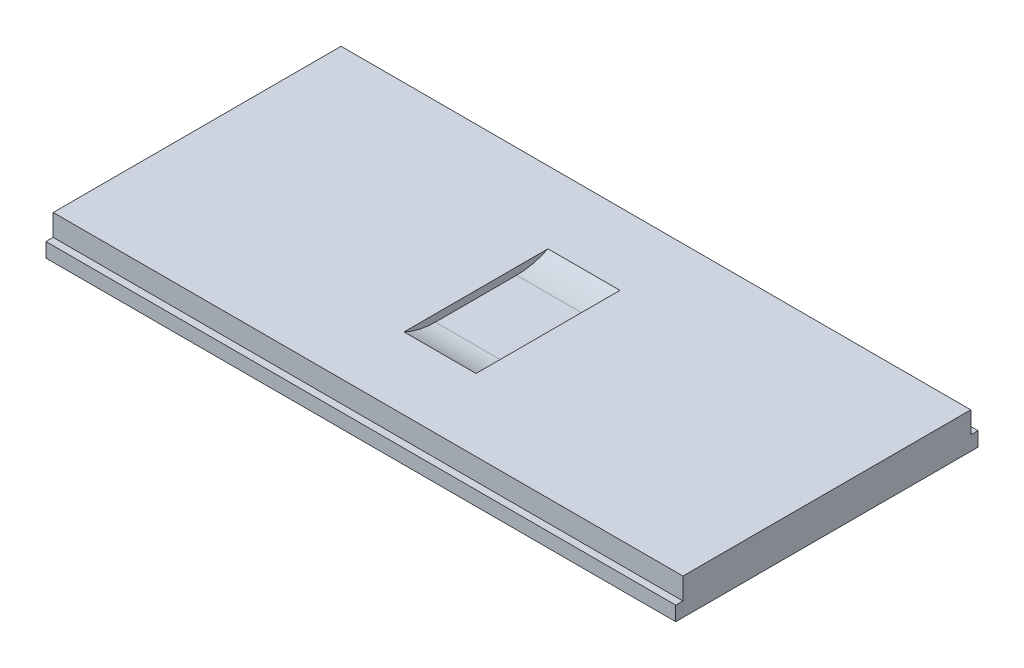
SolidWorks part; units mm, degrees
ref_plane "Front Plane" through (0, 0, 0) normal (0, 0, 1) x (1, 0, 0)
ref_plane "Top Plane" through (0, 0, 0) normal (0, 1, 0) x (1, 0, 0)
ref_plane "Right Plane" through (0, 0, 0) normal (1, 0, 0) x (0, 0, -1)
sketch "Sketch1" plane through (0, 0, 0) normal (0, 1, 0) x (1, 0, 0)
  line L1 (-43.75, 21) -> (43.75, 21)
  line L2 (-43.75, 21) -> (-43.75, -21)
  line L3 (-43.75, -21) -> (43.75, -21)
  line L4 (43.75, 21) -> (43.75, -21)
  line L5 (-43.75, 21) -> (43.75, -21) construction
  line L6 (-43.75, -21) -> (43.75, 21) construction
  point P0 (0, 0)
extrude "Boss-Extrude1" add sketch "Sketch1" along normal blind 5
sketch "Sketch2" plane through (0, 5, 0) normal (0, 1, 0) x (1, 0, 0)
  line L0 (-43.75, 21) -> (-43.75, -21) construction
  line L1 (43.75, 21) -> (-43.75, 21)
  line L2 (43.75, 21) -> (43.75, 20)
  line L3 (43.75, 20) -> (-43.75, 20)
  line L4 (-43.75, 21) -> (-43.75, 20)
extrude "Cut-Extrude1" cut sketch "Sketch2" against normal blind 3
sketch "Sketch3" plane through (0, 5, 0) normal (0, 1, 0) x (1, 0, 0)
  line L0 (43.75, -21) -> (43.75, 20) construction
  line L1 (-43.75, -21) -> (43.75, -21)
  line L2 (-43.75, -21) -> (-43.75, -20)
  line L3 (-43.75, -20) -> (43.75, -20)
  line L4 (43.75, -21) -> (43.75, -20)
extrude "Cut-Extrude2" cut sketch "Sketch3" against normal blind 3
sketch "Sketch4" plane through (0, 5, 0) normal (0, 1, 0) x (1, 0, 0)
  line L1 (-5, 10) -> (5, 10)
  line L2 (-5, 10) -> (-5, -10)
  line L3 (-5, -10) -> (5, -10)
  line L4 (5, 10) -> (5, -10)
  line L5 (-5, 10) -> (5, -10) construction
  line L6 (-5, -10) -> (5, 10) construction
  point P0 (0, 0)
extrude "Cut-Extrude3" cut sketch "Sketch4" against normal blind 1
fillet "Fillet1" radius 10 1 edges at (0, 4, 10)
fillet "Fillet2" radius 10 1 edges at (0, 4, -10)
